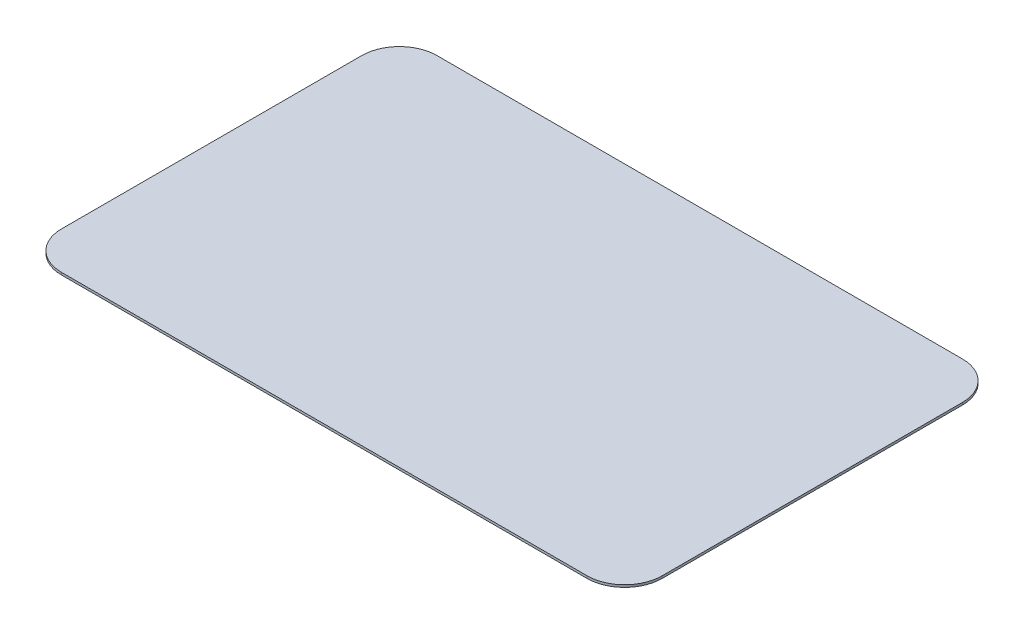
SolidWorks part; units mm, degrees
ref_plane "Front Plane" through (0, 0, 0) normal (0, 0, 1) x (1, 0, 0)
ref_plane "Top Plane" through (0, 0, 0) normal (0, 1, 0) x (1, 0, 0)
ref_plane "Right Plane" through (0, 0, 0) normal (1, 0, 0) x (0, 0, -1)
ref_plane "SheetPlane" through (0, 25.3275, 0) normal (0, 1, 0) x (1, 0, 0)
sketch "Sketch1" plane through (0, 25.3275, 0) normal (0, 1, 0) x (1, 0, 0)
  line L1 (-92.1192, -49.2656) -> (85.6808, -49.2656) construction
  line L2 (-104.8192, 65.0344) -> (-104.8192, -36.5656) construction
  line L3 (85.6808, 77.7344) -> (-92.1192, 77.7344) construction
  line L16 (98.3808, -36.5656) -> (98.3808, 65.0344)
  line L17 (-92.1192, -49.2656) -> (85.6808, -49.2656)
  line L18 (-104.8192, 65.0344) -> (-104.8192, -36.5656)
  line L19 (85.6808, 77.7344) -> (-92.1192, 77.7344)
  line L20 (98.3808, -36.5656) -> (98.3808, 65.0344) construction
  arc A0 (-92.1192, 77.7344) -> (-104.8192, 65.0344) centre (-92.1192, 65.0344) ccw construction
  arc A1 (-104.8192, -36.5656) -> (-92.1192, -49.2656) centre (-92.1192, -36.5656) ccw construction
  arc A2 (-92.1192, 77.7344) -> (-104.8192, 65.0344) centre (-92.1192, 65.0344) ccw
  arc A3 (85.6808, -49.2656) -> (98.3808, -36.5656) centre (85.6808, -36.5656) ccw construction
  arc A12 (85.6808, -49.2656) -> (98.3808, -36.5656) centre (85.6808, -36.5656) ccw
  arc A13 (98.3808, 65.0344) -> (85.6808, 77.7344) centre (85.6808, 65.0344) ccw construction
  arc A14 (98.3808, 65.0344) -> (85.6808, 77.7344) centre (85.6808, 65.0344) ccw
  arc A18 (-104.8192, -36.5656) -> (-92.1192, -49.2656) centre (-92.1192, -36.5656) ccw
extrude "MainBody" add sketch "Sketch1" along normal blind 0.7937
equation "\"SheetThickness\"= 0.03125in"
equation "\"D1@MainBody\" = \"SheetThickness\""
equation "\"SheetTolerance\"= 0.012in"
